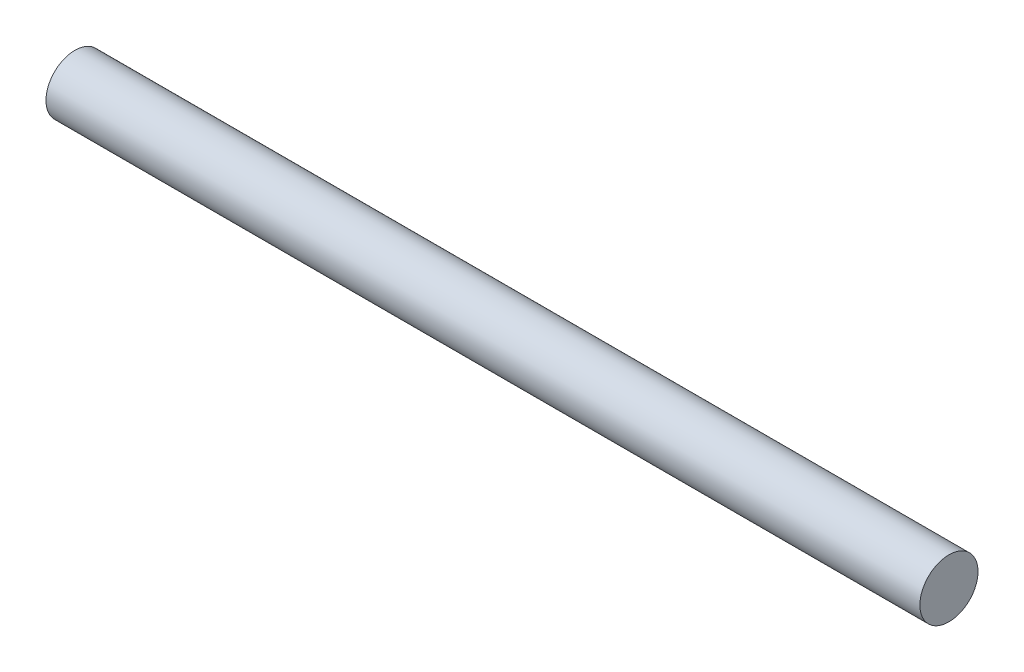
SolidWorks part; units mm, degrees
ref_plane "Front Plane" through (0, 0, 0) normal (0, 0, 1) x (1, 0, 0)
ref_plane "Top Plane" through (0, 0, 0) normal (0, 1, 0) x (1, 0, 0)
ref_plane "Right Plane" through (0, 0, 0) normal (1, 0, 0) x (0, 0, -1)
sketch "Sketch1" plane through (0, 0, 0) normal (0, 0, 1) x (1, 0, 0)
  line L0 (0, 0) -> (601.545, 0)
  point P4 (601.545, 0)
sketch "Sketch2" plane through (0, 0, 0) normal (1, 0, 0) x (0, 0, -1)
  circle A0 centre (0, 0) radius 20
  dimension "D1" = 40
sweep "Sweep1" add path "Sketch1" circular profile diameter 40 parameters "D3"=40
